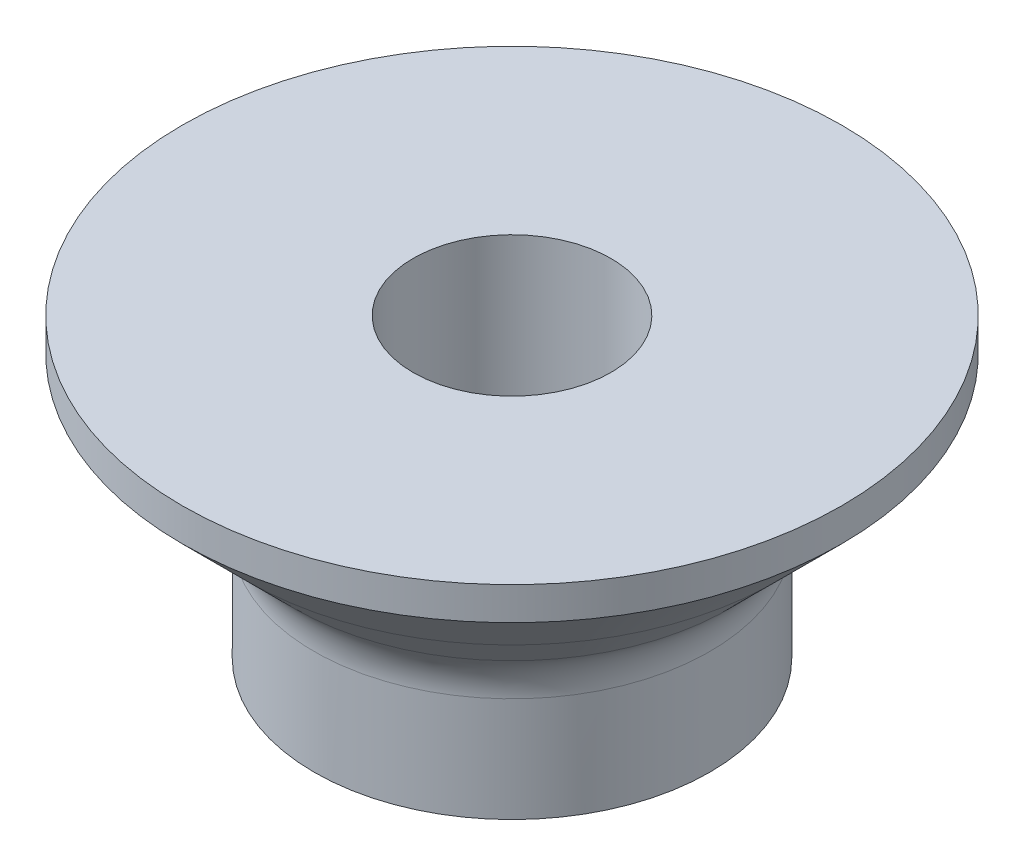
SolidWorks part; units mm, degrees
ref_plane "Front Plane" through (0, 0, 0) normal (0, 0, 1) x (1, 0, 0)
ref_plane "Top Plane" through (0, 0, 0) normal (0, 1, 0) x (1, 0, 0)
ref_plane "Right Plane" through (0, 0, 0) normal (1, 0, 0) x (0, 0, -1)
sketch "Sketch1" plane through (0, 0, 0) normal (0, 1, 0) x (1, 0, 0)
  circle A0 centre (0, 0) radius 6
  circle A1 centre (0, 0) radius 3
  dimension "D1" = 6
  dimension "D2" = 12
extrude "Boss-Extrude1" add sketch "Sketch1" along normal blind 9
sketch "Sketch2" plane through (0, 9, 0) normal (0, 1, 0) x (1, 0, 0)
  circle A0 centre (0, 0) radius 10
  circle A1 centre (0, 0) radius 3
  circle A2 centre (0, 0) radius 3 construction
  dimension "D1" = 20
extrude "Boss-Extrude2" add sketch "Sketch2" against normal blind 3
chamfer "Chamfer1" distance 2 angle 45 2 edges at (0, 6, 10) (0, 6, 6)
fillet "Fillet1" radius 2 1 edges at (0, 4, 6)
